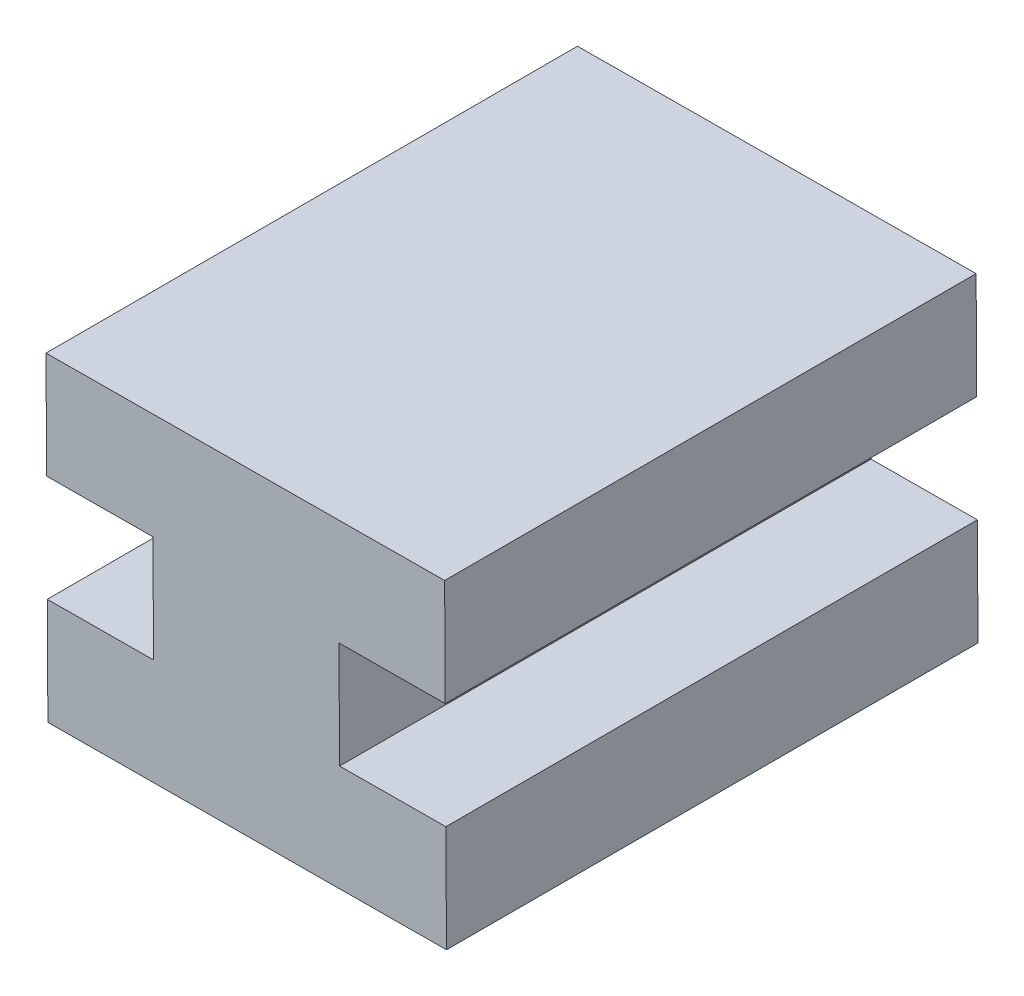
SolidWorks part; units mm, degrees
ref_plane "Front Plane" through (0, 0, 0) normal (0, 0, 1) x (1, 0, 0)
ref_plane "Top Plane" through (0, 0, 0) normal (0, 1, 0) x (1, 0, 0)
ref_plane "Right Plane" through (0, 0, 0) normal (1, 0, 0) x (0, 0, -1)
sketch "Sketch1" plane through (0, 0, 0) normal (0, 0, 1) x (1, 0, 0)
  line L12 (7.2745, 125.4559) -> (22.2743, 125.5446)
  line L13 (22.2743, 125.5446) -> (22.2506, 129.5445)
  line L14 (22.2506, 129.5445) -> (18.2507, 129.5208)
  line L15 (18.2507, 129.5208) -> (18.227, 133.5208)
  line L16 (18.227, 133.5208) -> (22.227, 133.5444)
  line L17 (22.227, 133.5444) -> (22.2033, 137.5443)
  line L18 (22.2033, 137.5443) -> (7.2036, 137.4557)
  line L19 (7.2036, 137.4557) -> (7.2272, 133.4557)
  line L20 (7.2272, 133.4557) -> (11.2272, 133.4794)
  line L21 (11.2272, 133.4794) -> (11.2508, 129.4794)
  line L22 (11.2508, 129.4794) -> (7.2509, 129.4558)
  line L23 (7.2509, 129.4558) -> (7.2745, 125.4559)
  line L24 (7.2745, 125.4559) -> (22.2743, 125.5446)
  line L25 (22.2743, 125.5446) -> (22.2506, 129.5445)
  line L26 (22.2506, 129.5445) -> (18.2507, 129.5208)
  line L27 (18.2507, 129.5208) -> (18.227, 133.5208)
  line L28 (18.227, 133.5208) -> (22.227, 133.5444)
  line L29 (22.227, 133.5444) -> (22.2033, 137.5443)
  line L30 (22.2033, 137.5443) -> (7.2036, 137.4557)
  line L31 (7.2036, 137.4557) -> (7.2272, 133.4557)
  line L32 (7.2272, 133.4557) -> (11.2272, 133.4794)
  line L33 (11.2272, 133.4794) -> (11.2508, 129.4794)
  line L34 (11.2508, 129.4794) -> (7.2509, 129.4558)
  line L35 (7.2509, 129.4558) -> (7.2745, 125.4559)
  dimension "D1" = 0
extrude "Boss-Extrude1" add sketch "Sketch1" along normal blind 10 and the other way blind 10
